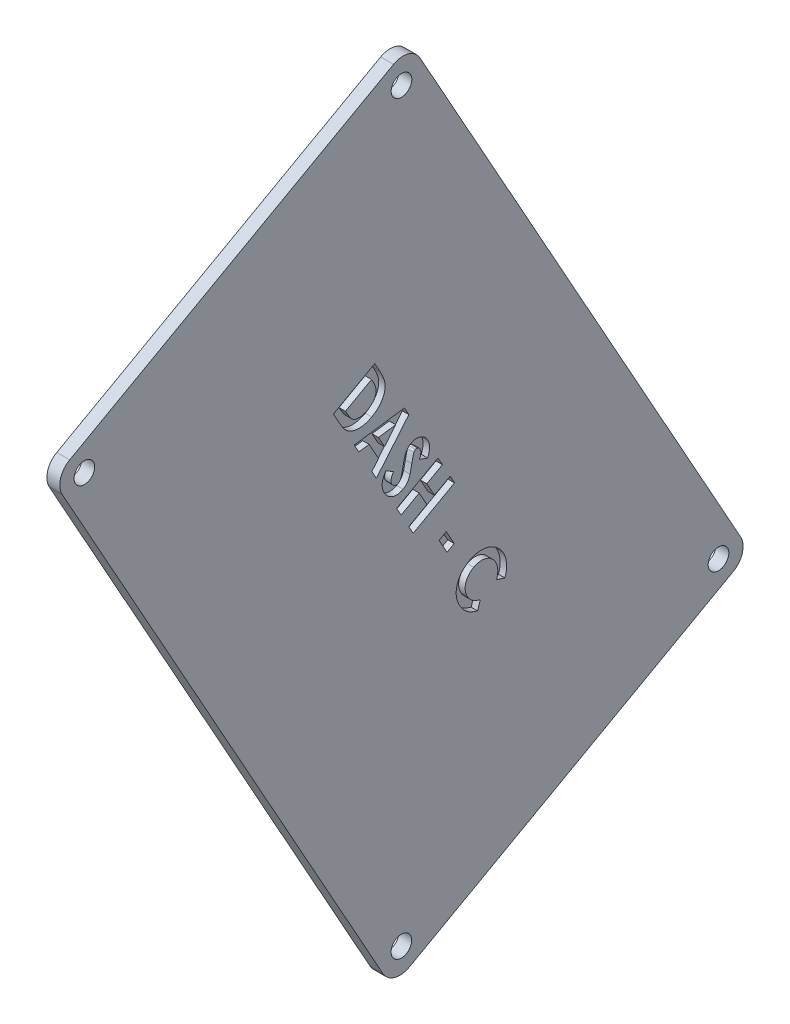
SolidWorks part; units mm, degrees
note: The reader was unsure of these and kept them because the rebuilt part matched: shared geometry of "Sketch1<3>", "Sketch1<5>".
ref_plane "Front Plane" through (0, 0, 0) normal (0, 0, 1) x (1, 0, 0)
ref_plane "Top Plane" through (0, 0, 0) normal (0, 1, 0) x (1, 0, 0)
ref_plane "Right Plane" through (0, 0, 0) normal (1, 0, 0) x (0, 0, -1)
sketch "Sketch1" plane through (0, 0, 0) normal (1, 0, 0) x (0, -1, 0)
  line L13 (60.4512, 149.7778) -> (49.9176, 168.6695)
  line L14 (-13.3228, 84.6734) -> (75.8869, 134.415)
  line L15 (77.0461, 138.4962) -> (49.044, 188.717)
  line L16 (44.9628, 189.8762) -> (-44.2469, 140.1347)
  line L17 (-45.4061, 136.0535) -> (-17.4039, 85.8327)
  line L18 (-13.3228, 84.6734) -> (75.8869, 134.415)
  line L19 (77.0461, 138.4962) -> (49.044, 188.717)
  line L21 (-45.4061, 136.0535) -> (-17.4039, 85.8327)
  line L24 (-16.6167, 110.7345) -> (-22.558, 121.3901)
  line L25 (-22.558, 121.3901) -> (-17.143, 124.4094)
  line L26 (-22.4707, 121.4388) -> (-13.7368, 126.3086) construction
  line L27 (-17.143, 124.4094) -> (-11.2017, 113.7538)
  line L32 (-16.5294, 110.7832) -> (-7.7954, 115.6531) construction
  line L33 (-11.2017, 113.7538) -> (-16.6167, 110.7345)
  line L38 (-13.3228, 84.6734) -> (75.8869, 134.415)
  line L39 (77.0461, 138.4962) -> (49.044, 188.717)
  line L40 (44.9628, 189.8762) -> (-44.2469, 140.1347)
  line L41 (-45.4061, 136.0535) -> (-17.4039, 85.8327)
  line L42 (-13.3228, 84.6734) -> (75.8869, 134.415)
  line L43 (77.0461, 138.4962) -> (49.044, 188.717)
  line L45 (-45.4061, 136.0535) -> (-17.4039, 85.8327)
  line L58 (44.9628, 189.8762) -> (-44.2469, 140.1347)
  line L59 (44.9628, 189.8762) -> (-44.2469, 140.1347)
  line L71 (60.4512, 149.7778) -> (66.3904, 153.0893)
  line L72 (49.9176, 168.6695) -> (55.8567, 171.981)
  line L73 (-8.2368, 90.0281) -> (68.6582, 132.9032)
  line L74 (-40.0514, 130.9675) -> (-18.9157, 93.0614)
  line L75 (39.8768, 184.5215) -> (-37.0181, 141.6464)
  line L76 (71.6914, 143.5821) -> (50.5557, 181.4883)
  line L77 (-8.2368, 90.0281) -> (68.6582, 132.9032)
  line L78 (-40.0514, 130.9675) -> (-18.9157, 93.0614)
  line L79 (39.8768, 184.5215) -> (-37.0181, 141.6464)
  line L80 (71.6914, 143.5821) -> (50.5557, 181.4883)
  line L81 (-13.6494, 126.3573) -> (-7.7081, 115.7018) construction
  arc A8 (75.8869, 134.415) -> (77.0461, 138.4962) centre (74.4259, 137.0352) ccw
  arc A9 (75.8869, 134.415) -> (77.0461, 138.4962) centre (74.4259, 137.0352) ccw
  arc A10 (49.044, 188.717) -> (44.9628, 189.8762) centre (46.4238, 187.256) ccw
  arc A11 (49.044, 188.717) -> (44.9628, 189.8762) centre (46.4238, 187.256) ccw
  arc A40 (75.8869, 134.415) -> (77.0461, 138.4962) centre (74.4259, 137.0352) ccw
  circle A45 centre (46.1919, 186.4398) radius 1.6 construction
  arc A48 (-44.2469, 140.1347) -> (-45.4061, 136.0535) centre (-42.7859, 137.5144) ccw
  arc A49 (-44.2469, 140.1347) -> (-45.4061, 136.0535) centre (-42.7859, 137.5144) ccw
  arc A50 (-17.4039, 85.8327) -> (-13.3228, 84.6734) centre (-14.7837, 87.2936) ccw
  arc A51 (-17.4039, 85.8327) -> (-13.3228, 84.6734) centre (-14.7837, 87.2936) ccw
  arc A52 (75.8869, 134.415) -> (77.0461, 138.4962) centre (74.4259, 137.0352) ccw
  arc A53 (49.044, 188.717) -> (44.9628, 189.8762) centre (46.4238, 187.256) ccw
  arc A54 (49.044, 188.717) -> (44.9628, 189.8762) centre (46.4238, 187.256) ccw
  arc A55 (-44.2469, 140.1347) -> (-45.4061, 136.0535) centre (-42.7859, 137.5144) ccw
  arc A56 (-44.2469, 140.1347) -> (-45.4061, 136.0535) centre (-42.7859, 137.5144) ccw
  arc A57 (-17.4039, 85.8327) -> (-13.3228, 84.6734) centre (-14.7837, 87.2936) ccw
  arc A58 (-17.4039, 85.8327) -> (-13.3228, 84.6734) centre (-14.7837, 87.2936) ccw
  arc A64 (71.0972, 140.1179) -> (71.6914, 143.5821) centre (69.2459, 142.2185) ccw
  arc A65 (71.0972, 140.1179) -> (71.6914, 143.5821) centre (69.2459, 142.2185) ccw
  arc A66 (68.6582, 132.9032) -> (69.9737, 136.1626) centre (67.2946, 135.3488) ccw
  arc A67 (68.6582, 132.9032) -> (69.9737, 136.1626) centre (67.2946, 135.3488) ccw
  arc A70 (-11.701, 90.6224) -> (-8.2368, 90.0281) centre (-9.6004, 92.4737) ccw
  arc A74 (-11.701, 90.6224) -> (-8.2368, 90.0281) centre (-9.6004, 92.4737) ccw
  arc A76 (-18.9157, 93.0614) -> (-15.6563, 91.7458) centre (-16.4701, 94.425) ccw
  arc A91 (-18.9157, 93.0614) -> (-15.6563, 91.7458) centre (-16.4701, 94.425) ccw
  arc A92 (-39.4572, 134.4317) -> (-40.0514, 130.9675) centre (-37.6059, 132.3311) ccw
  arc A93 (-39.4572, 134.4317) -> (-40.0514, 130.9675) centre (-37.6059, 132.3311) ccw
  arc A94 (-37.0181, 141.6464) -> (-38.3337, 138.387) centre (-35.6546, 139.2008) ccw
  arc A95 (-37.0181, 141.6464) -> (-38.3337, 138.387) centre (-35.6546, 139.2008) ccw
  arc A96 (43.341, 183.9273) -> (39.8768, 184.5215) centre (41.2404, 182.076) ccw
  arc A97 (43.341, 183.9273) -> (39.8768, 184.5215) centre (41.2404, 182.076) ccw
  arc A98 (50.5557, 181.4883) -> (47.2963, 182.8038) centre (48.1102, 180.1247) ccw
  arc A99 (50.5557, 181.4883) -> (47.2963, 182.8038) centre (48.1102, 180.1247) ccw
  circle A111 centre (73.6097, 137.267) radius 1.6 construction
  circle A112 centre (-14.5519, 88.1099) radius 1.6 construction
  circle A113 centre (-41.9696, 137.2826) radius 1.6 construction
  circle A118 centre (46.1919, 186.4398) radius 1.6
  circle A119 centre (73.6097, 137.267) radius 1.6
  circle A120 centre (-14.5519, 88.1099) radius 1.6
  circle A121 centre (-41.9696, 137.2826) radius 1.6
  arc A124 (71.0972, 140.1179) -> (69.9737, 136.1626) centre (73.6097, 137.267) ccw
  arc A127 (-11.701, 90.6224) -> (-15.6563, 91.7458) centre (-14.5519, 88.1099) ccw
  arc A130 (-39.4572, 134.4317) -> (-38.3337, 138.387) centre (-41.9696, 137.2826) ccw
  arc A133 (43.341, 183.9273) -> (47.2963, 182.8038) centre (46.1919, 186.4398) ccw
  arc A136 (71.0972, 140.1179) -> (69.9737, 136.1626) centre (73.6097, 137.267) ccw
  arc A139 (-11.701, 90.6224) -> (-15.6563, 91.7458) centre (-14.5519, 88.1099) ccw
  arc A142 (-39.4572, 134.4317) -> (-38.3337, 138.387) centre (-41.9696, 137.2826) ccw
  arc A145 (43.341, 183.9273) -> (47.2963, 182.8038) centre (46.1919, 186.4398) ccw
  dimension "D2" = 4
  dimension "D1" = 0
  dimension "D3" = 0
  dimension "D4" = 0.2
extrude "BASE" add sketch "Sketch1" along normal blind 2
extrude "Inside" add sketch "Sketch1<3>" against normal blind 1 from surface at 0
sketch "Sketch1<3>" plane through (0, 0, 0) normal (1, 0, 0) x (0, -1, 0) same geometry as "Sketch1"
sketch "Sketch2" plane through (2, 0, 0) normal (1, 0, 0) x (0, -1, 0)
  line L0 (-31.405, 110.9431) -> (63.045, 163.6066) construction
  line L3 (77.0461, 138.4962) -> (49.044, 188.717) construction
  line L4 (-17.4039, 85.8327) -> (-45.4061, 136.0535) construction
  text T0 "<b>DASH - C</b>" font "Century Gothic" height in points 28
extrude "Cut-Extrude1" cut sketch "Sketch2" against normal blind 1
extrude "Boss-Extrude3" add sketch "Sketch1<5>" against normal blind 0.254 from surface at -1 contours L33 L27 L25 L24 starting at face at (-1, -24.2868, -141.9957)
sketch "Sketch1<5>" plane through (0, 0, 0) normal (1, 0, 0) x (0, -1, 0) same geometry as "Sketch1"
